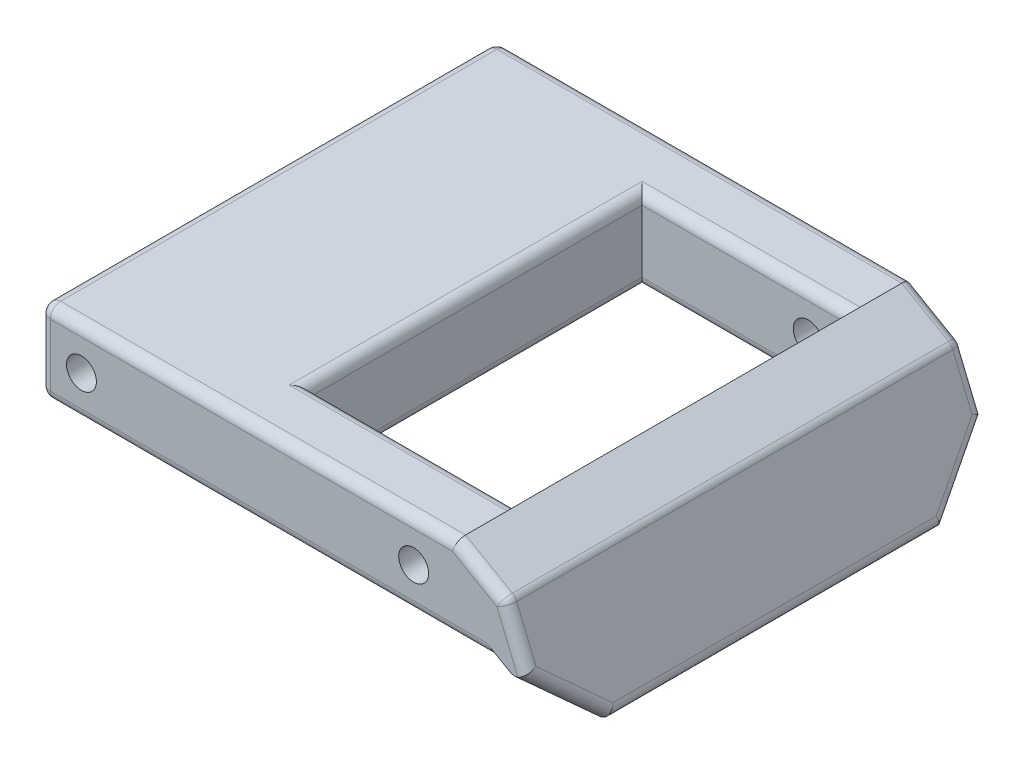
SolidWorks part; units mm, degrees
ref_plane "Front Plane" through (0, 0, 0) normal (0, 0, 1) x (1, 0, 0)
ref_plane "Top Plane" through (0, 0, 0) normal (0, 1, 0) x (1, 0, 0)
ref_plane "Right Plane" through (0, 0, 0) normal (1, 0, 0) x (0, 0, -1)
sketch "Sketch1" plane through (0, 0, 0) normal (0, 0, 1) x (1, 0, 0)
  line L0 (0, 0) -> (63.5, 0)
  line L1 (63.5, 0) -> (82.9448, -11.2265)
  line L2 (82.9448, -11.2265) -> (76.5948, -22.225)
  line L3 (76.5948, -22.225) -> (60.097, -12.7)
  line L4 (60.097, -12.7) -> (0, -12.7)
  line L5 (0, -12.7) -> (0, 0)
  dimension "D1" = 12.7
  dimension "D2" = 12.7
  dimension "D3" = 210
  dimension "D4" = 63.5
  dimension "D5" = 19.05
extrude "Boss-Extrude1" add sketch "Sketch1" along normal blind 69.85
sketch "Sketch2" plane through (0, 0, 0) normal (0, 0, -1) x (-1, 0, 0)
  line L1 (0, -12.7) -> (-60.097, -12.7) construction
  line L2 (0, 0) -> (0, -12.7) construction
  circle A0 centre (-6.35, -6.35) radius 2.286
  dimension "D1" = 4.572
  dimension "D3" = 6.35
  dimension "D2" = 6.35
extrude "Cut-Extrude1" cut sketch "Sketch2" against normal blind 12.7
sketch "Sketch3" plane through (67.0698, -38.7228, 0) normal (0.866, -0.5, 0) x (0, 0, -1)
  line L0 (-69.85, 24.5493) -> (-60.325, 19.05)
  line L1 (-69.85, 19.05) -> (-69.85, 31.75) construction
  line L2 (-69.85, 19.05) -> (0, 19.05) construction
  line L3 (-60.325, 19.05) -> (-69.85, 19.05)
  line L4 (-69.85, 19.05) -> (-69.85, 24.5493)
  line L5 (-34.925, 31.75) -> (-34.925, -10.9985) construction
  line L6 (-69.85, 31.75) -> (0, 31.75) construction
  line L7 (-69.85, -10.9985) -> (0, -10.9985) construction
  line L8 (-9.525, 19.05) -> (0, 19.05)
  line L9 (0, 24.5493) -> (-9.525, 19.05)
  line L10 (0, 19.05) -> (0, 24.5493)
  dimension "D1" = 30
  dimension "D2" = 50.8
extrude "Cut-Extrude2" cut sketch "Sketch3" against normal up to surface (19.05 mm away) up to face at (30.0485, -12.7, 34.925)
sketch "Sketch5" plane through (0, 0, 69.85) normal (0, 0, 1) x (1, 0, 0)
  line L0 (0, 0) -> (0, -12.7) construction
  line L1 (63.5, 0) -> (0, 0) construction
  line L2 (0, -12.7) -> (71.0956, -12.7) construction
  circle A0 centre (6.35, -6.35) radius 2.286
  circle A1 centre (57.15, -6.35) radius 2.286
  dimension "D1" = 4.572
  dimension "D2" = 6.35
  dimension "D3" = 6.35
  dimension "D6" = 4.572
  dimension "D4" = 50.8
  dimension "D5" = 6.35
extrude "Cut-Extrude4" cut sketch "Sketch5" against normal through all
sketch "Sketch6" plane through (0, 0, 0) normal (0, 1, 0) x (1, 0, 0)
  line L0 (63.5, -69.85) -> (63.5, 0) construction
  line L1 (63.5, -9.525) -> (31.75, -9.525)
  line L2 (63.5, -9.525) -> (63.5, -60.325)
  line L3 (63.5, -60.325) -> (31.75, -60.325)
  line L4 (31.75, -9.525) -> (31.75, -60.325)
  line L5 (63.5, -69.85) -> (0, -69.85) construction
  line L6 (63.5, 0) -> (0, 0) construction
  dimension "D1" = 31.75
  dimension "D2" = 9.525
  dimension "D3" = 9.525
extrude "Cut-Extrude5" cut sketch "Sketch6" against normal through all
chamfer "Chamfer1" distance 10.4775 distance2 13.6525 1 edges at (82.9448, -11.2265, 34.925) first distance on face at (79.628, -16.9713, 34.925)
fillet "Fillet1" radius 1.5875 23 edges at (73.3841, -9.8639, 69.85) (67.3107, -2.2001, 69.85) (31.75, 0, 69.85) (0, 0, 34.925) (0, -6.35, 69.85) (0, -12.7, 34.925) (0, -6.35, 0) (47.625, 0, 9.525) (31.75, 0, 34.925) (47.625, 0, 60.325) (45.9235, -12.7, 60.325) (31.75, -12.7, 34.925) (45.9235, -12.7, 9.525) (67.3107, -2.2001, 0) (73.3841, -9.8639, 0) (76.6764, -17.8139, 67.0122) (76.6764, -17.8139, 2.8378) (71.1214, -4.4002, 34.925) (76.5948, -22.225, 34.925) (77.7061, -20.3003, 34.925) (35.5478, -12.7, 0) (31.75, 0, 0) (35.5478, -12.7, 69.85)
